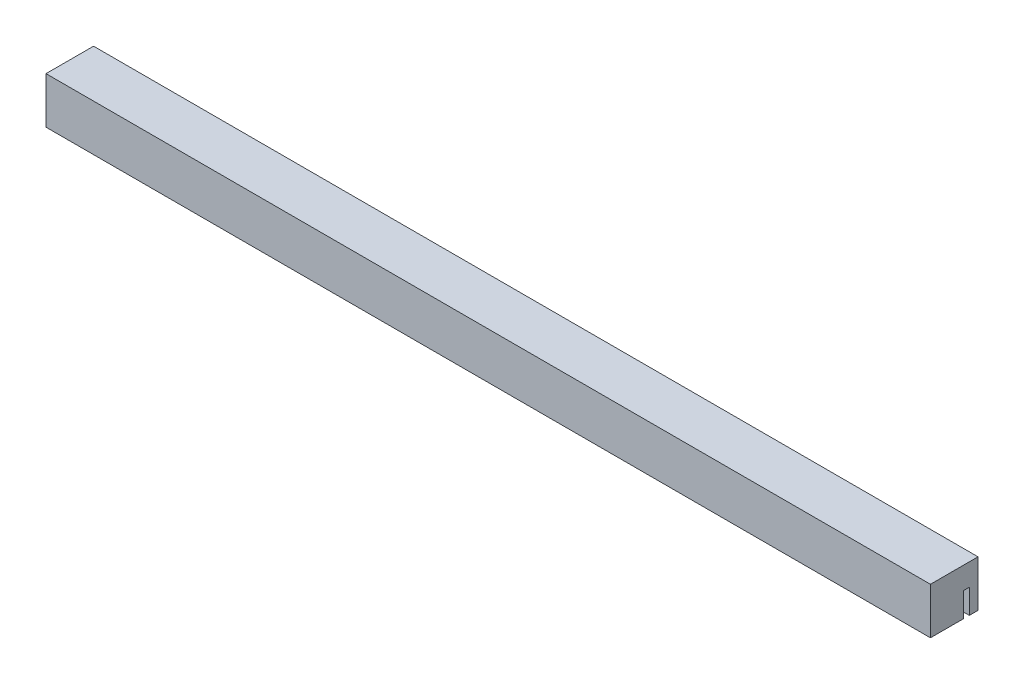
SolidWorks part; units mm, degrees
ref_plane "Front" through (0, 0, 0) normal (0, 0, 1) x (1, 0, 0)
ref_plane "Top" through (0, 0, 0) normal (0, 1, 0) x (1, 0, 0)
ref_plane "Right" through (0, 0, 0) normal (1, 0, 0) x (0, 0, -1)
ref_axis "Axis1" through (0, 0, 55) along (0, 0, -1)
sketch "Sketch1" plane through (0, 0, 0) normal (0, 0, 1) x (1, 0, 0)
  line L1 (-96.8375, 5.08) -> (96.8375, 5.08)
  line L2 (-96.8375, 5.08) -> (-96.8375, -5.08)
  line L3 (-96.8375, -5.08) -> (96.8375, -5.08)
  line L4 (96.8375, 5.08) -> (96.8375, -5.08)
  line L5 (-96.8375, 5.08) -> (96.8375, -5.08) construction
  line L6 (-96.8375, -5.08) -> (96.8375, 5.08) construction
  point P0 (0, 0)
  dimension "D1" = 193.675
  dimension "D2" = 10.16
extrude "Boss-Extrude1" add sketch "Sketch1" along normal blind 5.08
sketch "Sketch2" plane through (0, -5.08, 0) normal (0, -1, 0) x (1, 0, 0)
  line L0 (96.8375, 5.08) -> (96.8375, 0) construction
  line L1 (96.8375, 3.175) -> (-96.8375, 3.175)
  line L2 (96.8375, 3.175) -> (96.8375, 1.905)
  line L3 (96.8375, 1.905) -> (-96.8375, 1.905)
  line L4 (-96.8375, 3.175) -> (-96.8375, 1.905)
  line L5 (96.8375, 3.175) -> (-96.8375, 1.905) construction
  line L6 (96.8375, 1.905) -> (-96.8375, 3.175) construction
  line L7 (-96.8375, 5.08) -> (-96.8375, 0) construction
  point P4 (0, 2.54)
  dimension "D1" = 1.27
  dimension "D2" = 1.905
extrude "Cut-Extrude1" cut sketch "Sketch2" against normal blind 5.334
sketch "Sketch3" plane through (0, 0, 5.08) normal (0, 0, 1) x (1, 0, 0)
  line L4 (96.8375, -5.08) -> (96.8375, 5.08)
  line L5 (96.8375, 5.08) -> (-96.8375, 5.08)
  line L6 (-96.8375, 5.08) -> (-96.8375, -5.08)
  line L7 (-96.8375, -5.08) -> (96.8375, -5.08)
  line L8 (96.8375, -5.08) -> (96.8375, 5.08)
  line L9 (96.8375, 5.08) -> (-96.8375, 5.08)
  line L10 (-96.8375, 5.08) -> (-96.8375, -5.08)
  line L11 (-96.8375, -5.08) -> (96.8375, -5.08)
  dimension "D1" = 0
extrude "Boss-Extrude2" add sketch "Sketch3" along normal blind 5.334
